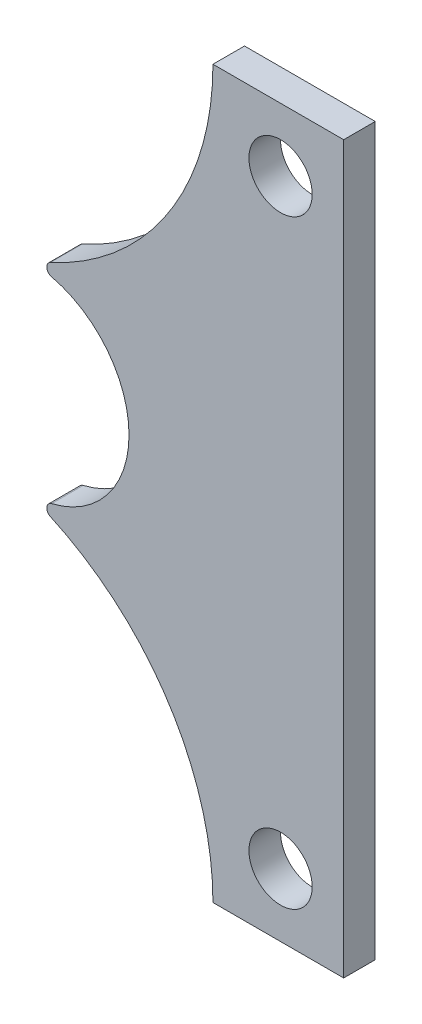
SolidWorks part; units mm, degrees
ref_plane "Front Plane" through (0, 0, 0) normal (0, 0, 1) x (1, 0, 0)
ref_plane "Top Plane" through (0, 0, 0) normal (0, 1, 0) x (1, 0, 0)
ref_plane "Right Plane" through (0, 0, 0) normal (1, 0, 0) x (0, 0, -1)
sketch "Sketch1" plane through (0, 0, 0) normal (0, 0, 1) x (1, 0, 0)
  line L0 (-7.2461, 73.025) -> (-7.2461, -73.025) construction
  line L1 (-19.05, -73.025) -> (19.05, -73.025)
  line L2 (-19.05, -73.025) -> (-19.05, 73.025)
  line L3 (-19.05, 73.025) -> (19.05, 73.025)
  line L4 (19.05, -73.025) -> (19.05, 73.025)
  line L5 (-19.05, -73.025) -> (19.05, 73.025) construction
  line L6 (-19.05, 73.025) -> (19.05, -73.025) construction
  line L7 (-44.45, 20.32) -> (-44.45, -20.32) construction
  line L8 (-44.45, 0) -> (0, 0) construction
  circle A0 centre (-44.45, 0) radius 52.07
  circle A1 centre (6.35, 60.325) radius 6.3627
  circle A2 centre (6.35, -60.325) radius 6.3627
  arc A3 (-7.2461, 73.025) -> (-19.05, 45.4546) centre (-45.3461, 73.025) cw
  circle A4 centre (-44.45, 0) radius 20.32
  arc A5 (-7.2461, 73.025) -> (-44.45, 20.32) centre (-63.1804, 73.025) cw
  arc A6 (-7.2461, -73.025) -> (-44.45, -20.32) centre (-63.1804, -73.025) ccw
  point P0 (0, 0)
  dimension "D2" = 104.14
  dimension "D3" = 12.7254
  dimension "D9" = 38.1
  dimension "D10" = 40.64
  dimension "D1" = 146.05
  dimension "D4" = 12.7
  dimension "D5" = 12.7
  dimension "D6" = 50.8
  dimension "D7" = 38.1
  dimension "D8" = 12.7
extrude "Boss-Extrude1" add sketch "Sketch1" along normal mid plane 6.35 contours A6 L2 A5 A4 | A6 A0 A5 L2 | A6 L1 L4 L3 A5 A0 A2 A1 region at (-7.9628, -57.2179, 0) region at (-7.9713, 0, 0) region at (-29.9637, -27.0142, 0)
fillet "Fillet1" radius 1.27 2 edges at (-44.45, -20.32, 0) (-44.45, 20.32, 0)
